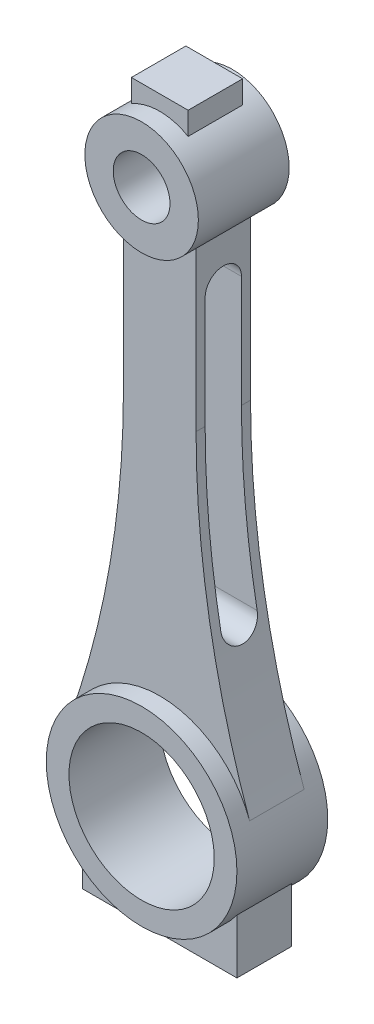
SolidWorks part; units mm, degrees
ref_plane "Front Plane" through (0, 0, 0) normal (0, 0, 1) x (1, 0, 0)
ref_plane "Top Plane" through (0, 0, 0) normal (0, 1, 0) x (1, 0, 0)
ref_plane "Right Plane" through (0, 0, 0) normal (1, 0, 0) x (0, 0, -1)
sketch "Sketch1" plane through (0, 0, 0) normal (0, 0, 1) x (1, 0, 0)
  line L0 (0, 148.822) -> (0, -30.2424) construction
  line L1 (-8, 75.3953) -> (-8, 110.3953)
  line L2 (8, 75.3953) -> (8, 110.3953)
  line L3 (6.25, 135.8253) -> (-6.25, 135.8253)
  line L4 (-6.25, 135.8253) -> (-6.25, 130.8253)
  line L5 (6.25, 135.8253) -> (6.25, 130.8253)
  line L6 (-17, -24.3288) -> (17, -24.3288)
  line L7 (17, -24.3288) -> (17, -12.3288)
  line L8 (-17, -24.3288) -> (-17, -12.3288)
  circle A0 centre (0, 0) radius 21
  circle A1 centre (0, 0) radius 16
  circle A2 centre (0, 120) radius 12.5
  circle A3 centre (0, 120) radius 6.25
  arc A4 (-8, 75.3953) -> (-19.7874, 7.0327) centre (-212.1328, 75.3953) cw
  arc A5 (8, 75.3953) -> (19.7874, 7.0327) centre (212.1328, 75.3953) ccw
  arc A6 (8, 75.3953) -> (19.7874, 7.0327) centre (212.1328, 75.3953) ccw
  dimension "D2" = 42
  dimension "D3" = 32
  dimension "D4" = 25
  dimension "D5" = 12.5
  dimension "D1" = 120
  dimension "D6" = 35
  dimension "D7" = 8
  dimension "D8" = 12.5
  dimension "D9" = 5
  dimension "D10" = 34
  dimension "D11" = 12
extrude "Boss-Extrude1" add sketch "Sketch1" along normal mid plane 20 contours A0 L0 A1 | L0 A0 A1 | L0 A2 A3 | A2 L0 A3 region at (3.1629, 131.8041, 0) region at (-0.2795, 129.375, 0) region at (11.8394, 16.7728, 0) region at (-0.4696, 18.5, 0)
extrude "Boss-Extrude2" add sketch "Sketch1<4>" along normal mid plane 12 contours L0 A2 L1 A4 A0 | A2 L0 A0 A5 L2 | L3 L0 A2 L5 | L0 L3 L4 A2 | A0 L0 L6 L7 | L0 A0 L8 L6 region at (3.3472, 133.8599, 0) region at (-3.3472, 133.8599, 0) region at (-5.3967, 57.8448, 0) region at (5.3967, 57.8448, 0) region at (-10.4494, -20.8498, 0) region at (10.4494, -20.8498, 0)
sketch "Sketch1<4>" plane through (0, 0, 0) normal (0, 0, 1) x (1, 0, 0) same geometry as "Sketch1"
sketch "Sketch2" plane through (0, 0, 0) normal (1, 0, 0) x (0, 0, -1)
  line L0 (0, 100) -> (0, 38) construction
  line L1 (4, 100) -> (4, 38)
  line L2 (-4, 100) -> (-4, 38)
  line L4 (-10, 120) -> (16.6623, 120) construction
  line L5 (-10, 132.5) -> (-10, 107.5) construction
  arc A0 (4, 100) -> (-4, 100) centre (0, 100) ccw
  arc A1 (-4, 38) -> (4, 38) centre (0, 38) ccw
  point P3 (0, 69)
  dimension "D2" = 4
  dimension "D1" = 62
  dimension "D3" = 20
extrude "Cut-Extrude1" cut sketch "Sketch2" against normal through all and the other way through all from offset 6
